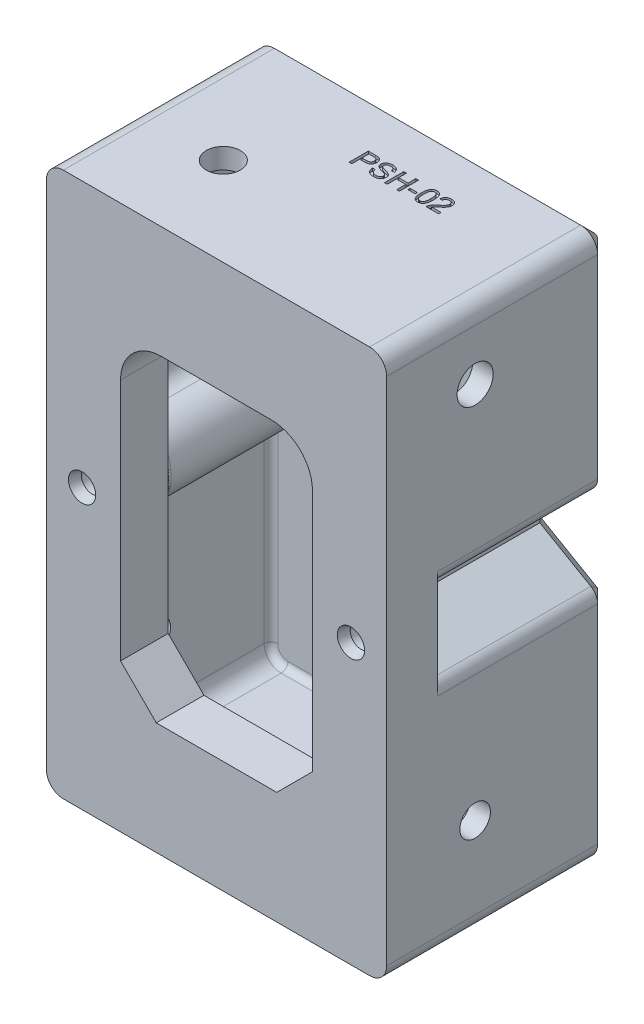
SolidWorks part; units mm, degrees
ref_plane "Front" through (0, 0, 0) normal (0, 0, 1) x (1, 0, 0)
ref_plane "Top" through (0, 0, 0) normal (0, 1, 0) x (1, 0, 0)
ref_plane "Right" through (0, 0, 0) normal (1, 0, 0) x (0, 0, -1)
sketch "Sketch3" plane through (0, 0, 0) normal (0, 0, 1) x (1, 0, 0)
  line L0 (10.9, 16.5) -> (0, 16.5) construction
  line L1 (0, 0) -> (50, 0)
  line L2 (0, 0) -> (0, 80)
  line L3 (0, 80) -> (50, 80)
  line L4 (50, 0) -> (50, 80)
  line L5 (10.9, 16.5) -> (39.1, 16.5)
  line L6 (10.9, 16.5) -> (10.9, 63.5)
  line L7 (10.9, 63.5) -> (39.1, 63.5)
  line L8 (39.1, 16.5) -> (39.1, 63.5)
  line L9 (39.1, 16.5) -> (50, 16.5) construction
  line L10 (10.9, 16.5) -> (10.9, 0) construction
  line L11 (10.9, 63.5) -> (10.9, 80) construction
  line L12 (25, 63.5) -> (25, 41) construction
  line L13 (25, 41) -> (25, 16.5) construction
  line L14 (25, 41) -> (5.25, 41) construction
  line L15 (25, 41) -> (44.75, 41) construction
  circle A0 centre (5.25, 41) radius 1.6 construction
  circle A1 centre (44.75, 41) radius 1.6 construction
  dimension "D5" = 39.5
  dimension "D6" = 3.2
  dimension "D1" = 50
  dimension "D2" = 80
  dimension "D3" = 28.2
  dimension "D4" = 22.5
  dimension "D7" = 24.5
extrude "Boss-Extrude1" add sketch "Sketch3" along normal blind 30
sketch "Sketch17" plane through (0, 0, 30) normal (0, 0, 1) x (1, 0, 0)
  circle A0 centre (44.75, 41) radius 1.6 construction
  circle A1 centre (5.25, 41) radius 1.6 construction
  circle A2 centre (44.75, 41) radius 1.6
  circle A3 centre (5.25, 41) radius 1.6
extrude "Cut-Extrude7" cut sketch "Sketch17" against normal through all
chamfer "Chamfer1" distance 0.4 angle 75 2 edges at (46.35, 41, 30) (6.85, 41, 30) first distance on face at (46.35, 41, 30)
sketch "Sketch4" plane through (0, 0, 0) normal (0, 0, -1) x (-1, 0, 0)
  line L4 (-47, 36.2566) -> (-47, 3)
  line L5 (-3, 45.7434) -> (-3, 77)
  line L8 (-47, 3) -> (-3, 3)
  line L9 (-3, 3) -> (-3, 77)
  line L10 (-47, 77) -> (-47, 3)
  line L11 (-3, 77) -> (-47, 77)
  line L12 (-47, 3) -> (-3, 3)
  line L13 (-3, 3) -> (-3, 36.2566)
  line L14 (-47, 77) -> (-47, 45.7434)
  line L15 (-3, 77) -> (-47, 77)
  arc A0 (-47, 36.2566) -> (-47, 45.7434) centre (-44.75, 41) ccw
  arc A1 (-3, 45.7434) -> (-3, 36.2566) centre (-5.25, 41) ccw
  dimension "D2" = 10.5
  dimension "D1" = 3
extrude "Cut-Extrude1" cut sketch "Sketch4" against normal offset from surface (23 mm away) 7 up to face at (42.75, 41, 30)
fillet "Fillet1" radius 2.5 4 edges at (0, 0, 15) (50, 0, 15) (50, 80, 15) (0, 80, 15)
fillet "Fillet2" radius 2.5 8 edges at (3, 3, 11.5) (47, 77, 11.5) (3, 36.2566, 11.5) (3, 45.7434, 11.5) (47, 36.2566, 11.5) (47, 45.7434, 11.5) (47, 3, 11.5) (3, 77, 11.5)
sketch "Sketch5" plane through (0, 0, 0) normal (-1, 0, 0) x (0, 0, 1)
  line L1 (0, 80) -> (30, 80) construction
  line L2 (17, 70) -> (17, 45) construction
  line L3 (17, 45) -> (17, 14.5) construction
  line L4 (30, 77.5) -> (30, 2.5) construction
  circle A0 centre (17, 70) radius 2.5
  circle A2 centre (17, 14.5) radius 2.25
  dimension "D1" = 13
  dimension "D2" = 5
  dimension "D3" = 10
  dimension "D4" = 25
  dimension "D5" = 14.5
  dimension "D6" = 4.5
extrude "Cut-Extrude2" cut sketch "Sketch5" against normal up to next
hole_wizard "M5 Clearance Hole1" positions "Sketch6" profile "Sketch7" hole size "M5" standard "ANSI Metric" end condition up to next
sketch "Sketch6" plane through (47, 0, 0) normal (-1, 0, 0) x (0, 0, 1)
  point P0 (17, 70)
sketch "Sketch7" plane through (47, 70, 17) normal (0, 1, 0) x (0, 0, 1)
  line L0 (0, 0) -> (0, 3)
  line L1 (0, 3) -> (2.65, 3)
  line L2 (2.65, 3) -> (2.65, 0)
  line L5 (2.65, 0) -> (0, 0)
  line L11 (0, -6.35) -> (0, 107.95) construction
  dimension "Thru Hole Dia." = 5.3
  dimension "Thru Hole Depth" = 3
sketch "Sketch8" plane through (0, 80, 0) normal (0, 1, 0) x (1, 0, 0)
  line L1 (0, -30) -> (0, 0) construction
  line L2 (47.5, -30) -> (2.5, -30) construction
  circle A0 centre (13, -17) radius 2.5
  dimension "D1" = 5
  dimension "D3" = 13
  dimension "D2" = 13
extrude "Cut-Extrude3" cut sketch "Sketch8" against normal up to surface (77 mm away) up to face at (25, 3, 11.5)
hole_wizard "M5 Clearance Hole2" positions "Sketch10" profile "Sketch11" hole size "M5" standard "ANSI Metric" end condition up to next
sketch "Sketch10" plane through (0, 3, 0) normal (0, 1, 0) x (1, 0, 0)
  point P0 (13, -17)
sketch "Sketch11" plane through (13, 3, 17) normal (1, 0, 0) x (0, 0, 1)
  line L0 (0, 0) -> (0, 3)
  line L1 (0, 3) -> (2.65, 3)
  line L2 (2.65, 3) -> (2.65, 0)
  line L5 (2.65, 0) -> (0, 0)
  line L11 (0, -6.35) -> (0, 107.95) construction
  dimension "Thru Hole Dia." = 5.3
  dimension "Thru Hole Depth" = 3
sketch "Sketch12" plane through (47, 0, 0) normal (-1, 0, 0) x (0, 0, 1)
  circle A0 centre (17, 14.5) radius 2.25 construction
  circle A1 centre (17, 14.5) radius 2.25
extrude "Cut-Extrude4" cut sketch "Sketch12" against normal through all
sketch "Sketch13" plane through (0, 80, 0) normal (0, 1, 0) x (1, 0, 0)
  line L0 (8, -8) -> (50, -8) construction
  line L1 (50, 0) -> (50, -30) construction
  line L2 (47.5, 0) -> (2.5, 0) construction
  text T0 "PSH-02"
  dimension "D1" = 8
extrude "Part Number" cut sketch "Sketch13" against normal blind 0.4
sketch "Sketch14" plane through (0, 0, 30) normal (0, 0, 1) x (1, 0, 0)
  line L1 (10.25, 68.5) -> (39.75, 68.5)
  line L2 (10.25, 68.5) -> (10.25, 11.5)
  line L3 (10.25, 11.5) -> (39.75, 11.5)
  line L4 (39.75, 68.5) -> (39.75, 11.5)
  line L6 (25, 68.5) -> (25, 63.5) construction
  line L7 (39.1, 63.5) -> (10.9, 63.5) construction
  line L8 (25, 11.5) -> (25, 16.5) construction
  line L9 (10.9, 16.5) -> (39.1, 16.5) construction
  dimension "D1" = 57
  dimension "D2" = 29.5
extrude "Omnicom Enlarged Socket Cavity" [suppressed] cut sketch "Sketch14" against normal through all
sketch "Sketch15" [suppressed] plane through (0, 0, 23) normal (0, 0, 1) x (1, 0, 0)
  line L0 (25, 40) -> (39.1, 40) construction
  line L1 (10, 9.5) -> (40, 9.5)
  line L2 (10, 9.5) -> (10, 70.5)
  line L3 (10, 70.5) -> (40, 70.5)
  line L4 (40, 9.5) -> (40, 70.5)
  line L5 (10, 9.5) -> (40, 70.5) construction
  line L6 (10, 70.5) -> (40, 9.5) construction
  line L7 (39.1, 16.4) -> (39.1, 63.6) construction
  line L8 (25, 40) -> (10.9, 40) construction
  line L9 (10.9, 63.6) -> (10.9, 16.4) construction
  point P0 (25, 40)
  dimension "D1" = 61
  dimension "D2" = 30
extrude "Astrodyne Enlarged Socket Cavity" [suppressed] cut sketch "Sketch15" against normal through all
sketch "Sketch16" [suppressed] plane through (0, 0, 23) normal (0, 0, 1) x (1, 0, 0)
  line L0 (25, 76) -> (25, 70.5) construction
  line L1 (40, 70.5) -> (10, 70.5) construction
  line L2 (25, 4) -> (25, 9.5) construction
  line L3 (10, 9.5) -> (40, 9.5) construction
  circle A0 centre (25, 76) radius 1.4
  circle A1 centre (25, 4) radius 1.4
  dimension "D1" = 72
  dimension "D2" = 2.8
extrude "Cut-Extrude6" [suppressed] cut sketch "Sketch16" against normal through all
chamfer "Chamfer2" [suppressed] distance 0.4 angle 70
ref_plane "Plane1" [suppressed] through (0, 0, 10) normal (0, 0, 1) x (1, 0, 0)
sketch "Sketch18" [suppressed] plane through (0, 0, 10) normal (0, 0, 1) x (1, 0, 0)
  line L0 (47, 70) -> (46.2, 70) construction
  line L1 (47, 72.65) -> (47, 67.35) construction
  line L2 (46.2, 70) -> (-6.9259, 84.235) construction
  line L3 (46.2, 70) -> (26.1844, 70) construction
  dimension "D1" = 15
  dimension "D2" = 55
  dimension "D3" = 0.8
ref_plane "Plane2" [suppressed] through (-6.9259, 84.235, 10) normal (-0.9659, 0.2588, 0) x (0, 0, 1)
sketch "Sketch19" [suppressed] plane through (-6.9259, 84.235, 10) normal (-0.9659, 0.2588, 0) x (0, 0, 1)
  line L0 (0, 0) -> (0, -5.1804) construction
  circle A0 centre (0, 0) radius 2
  dimension "D1" = 4
extrude "Cut-Extrude8" [suppressed] cut sketch "Sketch19" against normal up to surface (56.3641 mm away)
chamfer "Chamfer3" distance 5.25 2 edges at (39.1, 16.5, 26.5) (10.9, 16.5, 26.5)
fillet "Fillet3" radius 6 2 edges at (39.1, 63.5, 26.5) (10.9, 63.5, 26.5)
sketch "Sketch22" plane through (0, 0, 0) normal (0, 0, -1) x (-1, 0, 0)
  line L0 (-33.5, 40) -> (-16.5, 40) construction
  line L1 (-33.5, 42.5) -> (-16.5, 42.5)
  line L2 (-33.5, 37.5) -> (-16.5, 37.5)
  line L3 (-25, 0) -> (-25, 80) construction
  line L4 (-47.5, 0) -> (-2.5, 0)
  line L5 (0, 2.5) -> (0, 77.5)
  line L6 (-2.5, 80) -> (-47.5, 80)
  line L7 (-50, 77.5) -> (-50, 2.5)
  line L8 (-47.5, 0) -> (-2.5, 0)
  line L9 (0, 2.5) -> (0, 77.5)
  line L10 (-2.5, 80) -> (-47.5, 80)
  line L11 (-50, 77.5) -> (-50, 2.5)
  arc A0 (-33.5, 42.5) -> (-33.5, 37.5) centre (-33.5, 40) ccw
  arc A1 (-16.5, 37.5) -> (-16.5, 42.5) centre (-16.5, 40) ccw
  arc A4 (-2.5, 0) -> (0, 2.5) centre (-2.5, 2.5) ccw
  arc A5 (0, 77.5) -> (-2.5, 80) centre (-2.5, 77.5) ccw
  arc A6 (-47.5, 80) -> (-50, 77.5) centre (-47.5, 77.5) ccw
  arc A7 (-50, 2.5) -> (-47.5, 0) centre (-47.5, 2.5) ccw
  arc A8 (-2.5, 0) -> (0, 2.5) centre (-2.5, 2.5) ccw
  arc A9 (0, 77.5) -> (-2.5, 80) centre (-2.5, 77.5) ccw
  arc A10 (-47.5, 80) -> (-50, 77.5) centre (-47.5, 77.5) ccw
  arc A11 (-50, 2.5) -> (-47.5, 0) centre (-47.5, 2.5) ccw
  point P12 (-25, 40)
  dimension "D2" = 5
  dimension "D3" = 17
  dimension "D4" = 40
  dimension "D1" = 0
extrude "Boss-Extrude2" add sketch "Sketch22" along normal blind 3
sketch "Sketch21" plane through (0, 0, 23) normal (0, 0, -1) x (-1, 0, 0)
  line L1 (-42, 39.4123) -> (-42, 42.5877)
  line L2 (-42, 42.5877) -> (-44.75, 44.1754)
  line L3 (-44.75, 44.1754) -> (-47.5, 42.5877)
  line L4 (-47.5, 42.5877) -> (-47.5, 39.4123)
  line L5 (-47.5, 39.4123) -> (-44.75, 37.8246)
  line L6 (-44.75, 37.8246) -> (-42, 39.4123)
  line L7 (-8, 39.4123) -> (-5.25, 37.8246)
  line L8 (-5.25, 37.8246) -> (-2.5, 39.4123)
  line L9 (-2.5, 39.4123) -> (-2.5, 42.5877)
  line L10 (-2.5, 42.5877) -> (-5.25, 44.1754)
  line L11 (-5.25, 44.1754) -> (-8, 42.5877)
  line L12 (-8, 42.5877) -> (-8, 39.4123)
  circle A0 centre (-44.75, 41) radius 2.75 construction
  circle A1 centre (-5.25, 41) radius 2.75 construction
  dimension "D1" = 5.5
extrude "Cut-Extrude9" cut sketch "Sketch21" against normal blind 2.5 and the other way through all
sketch "Sketch23" plane through (0, 0, -3) normal (0, 0, -1) x (-1, 0, 0)
  line L5 (-50, 77.5) -> (-50, 2.5) construction
  line L6 (-50, 47.7839) -> (-50, 34.2161)
  line L8 (-41.5, 42.8764) -> (-44.5, 44.6084)
  line L9 (-41.5, 39.1236) -> (-41.5, 42.8764)
  line L10 (-44.5, 37.3916) -> (-41.5, 39.1236)
  line L11 (-41.5, 42.8764) -> (-50, 47.7839)
  line L12 (-41.5, 39.1236) -> (-41.5, 42.8764)
  line L13 (-50, 34.2161) -> (-41.5, 39.1236)
  line L19 (0, 2.5) -> (0, 77.5) construction
  line L20 (0, 47.7839) -> (0, 34.2161)
  line L22 (-8.5, 39.1236) -> (-5.5, 37.3916)
  line L23 (-8.5, 42.8764) -> (-8.5, 39.1236)
  line L24 (-5.5, 44.6084) -> (-8.5, 42.8764)
  line L25 (-8.5, 39.1236) -> (0, 34.2161)
  line L26 (-8.5, 42.8764) -> (-8.5, 39.1236)
  line L27 (0, 47.7839) -> (-8.5, 42.8764)
  dimension "D1" = 0.5
  dimension "D2" = 0.5
extrude "Cut-Extrude10" cut sketch "Sketch23" against normal offset from surface (25.5 mm away) 3 up to face at (44.75, 41, 25.5)
fillet "Fillet5" radius 2 4 edges at (50, 47.7839, 9.75) (50, 34.2161, 9.75) (0, 47.7839, 9.75) (0, 34.2161, 9.75)
chamfer "Chamfer5" distance 2 angle 45 18 edges at (25, 0, -3) (0.7322, 0.7322, -3) (49.2678, 0.7322, -3) (0.7322, 79.2678, -3) (49.2678, 79.2678, -3) (25, 80, -3) (0, 63.2193, -3) (45.25, 45.0415, -3) (41.5, 41, -3) (45.25, 36.9585, -3) (4.75, 45.0415, -3) (4.75, 36.9585, -3) (8.5, 41, -3) (50, 17.7807, -3) (49.7321, 34.0614, -3) (0.2679, 34.0614, -3) (0.2679, 47.9386, -3) (49.7321, 47.9386, -3)
fillet "Fillet4" radius 1 32 edges at (3.7322, 76.2678, 23) (25, 77, 23) (46.2678, 76.2678, 23) (47, 61.623, 23) (46.2961, 47.0069, 23) (39.5, 41, 23) (46.2961, 34.9931, 23) (47, 19.377, 23) (46.2678, 3.7322, 23) (25, 3, 23) (3.7322, 3.7322, 23) (3, 19.377, 23) (3.7039, 34.9931, 23) (10.5, 41, 23) (3.7039, 47.0069, 23) (3.7322, 76.2678, 0) (3, 61.623, 0) (3.7039, 47.0069, 0) (10.5, 41, 0) (3.7039, 34.9931, 0) (3, 19.377, 0) (3.7322, 3.7322, 0) (25, 3, 0) (46.2678, 3.7322, 0) (47, 19.377, 0) (46.2961, 34.9931, 0) (39.5, 41, 0) (46.2961, 47.0069, 0) (47, 61.623, 0) (46.2678, 76.2678, 0) (3, 61.623, 23) (25, 77, 0)
